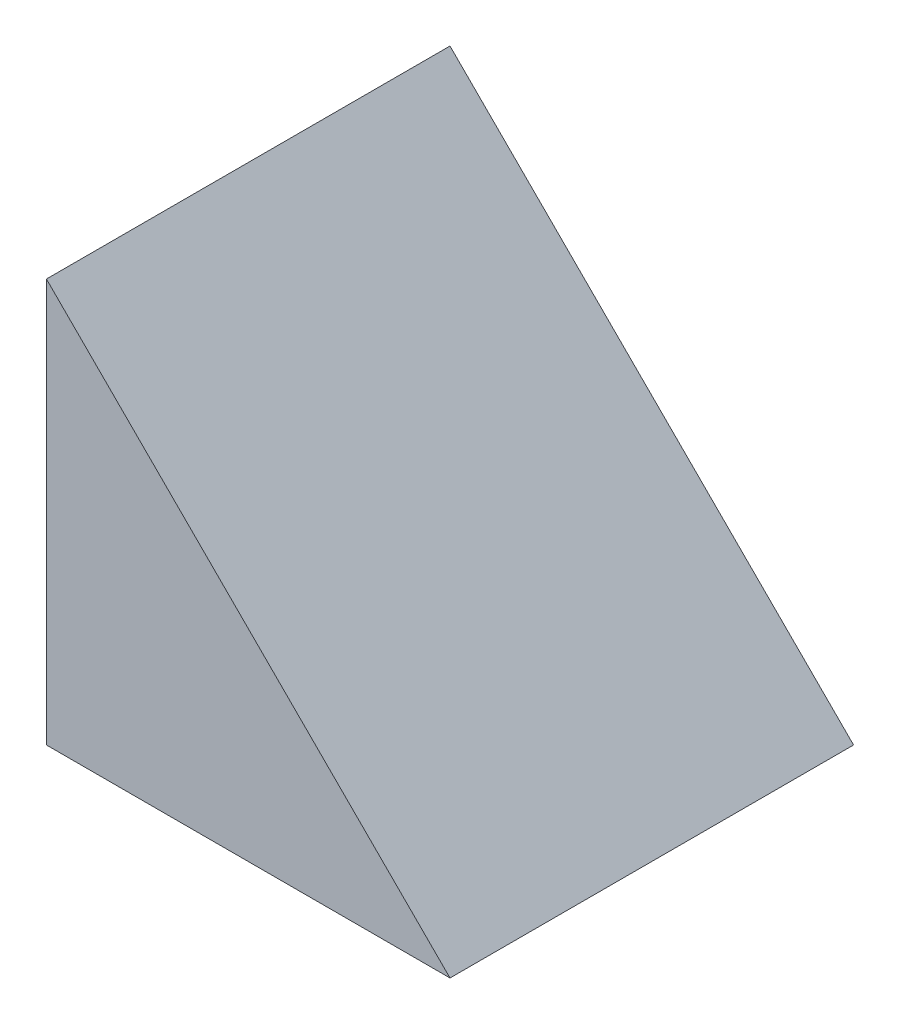
SolidWorks part; units mm, degrees
ref_plane "Front Plane" through (0, 0, 0) normal (0, 0, 1) x (1, 0, 0)
ref_plane "Top Plane" through (0, 0, 0) normal (0, 1, 0) x (1, 0, 0)
ref_plane "Right Plane" through (0, 0, 0) normal (1, 0, 0) x (0, 0, -1)
sketch "Sketch1" plane through (0, 0, 0) normal (0, 0, 1) x (1, 0, 0)
  line L0 (0, 0) -> (25.4, 0)
  line L1 (25.4, 0) -> (0, 25.4)
  line L2 (0, 25.4) -> (0, 0)
  dimension "D1" = 25.4
  dimension "D2" = 25.4
extrude "Boss-Extrude1" add sketch "Sketch1" along normal blind 25.4
